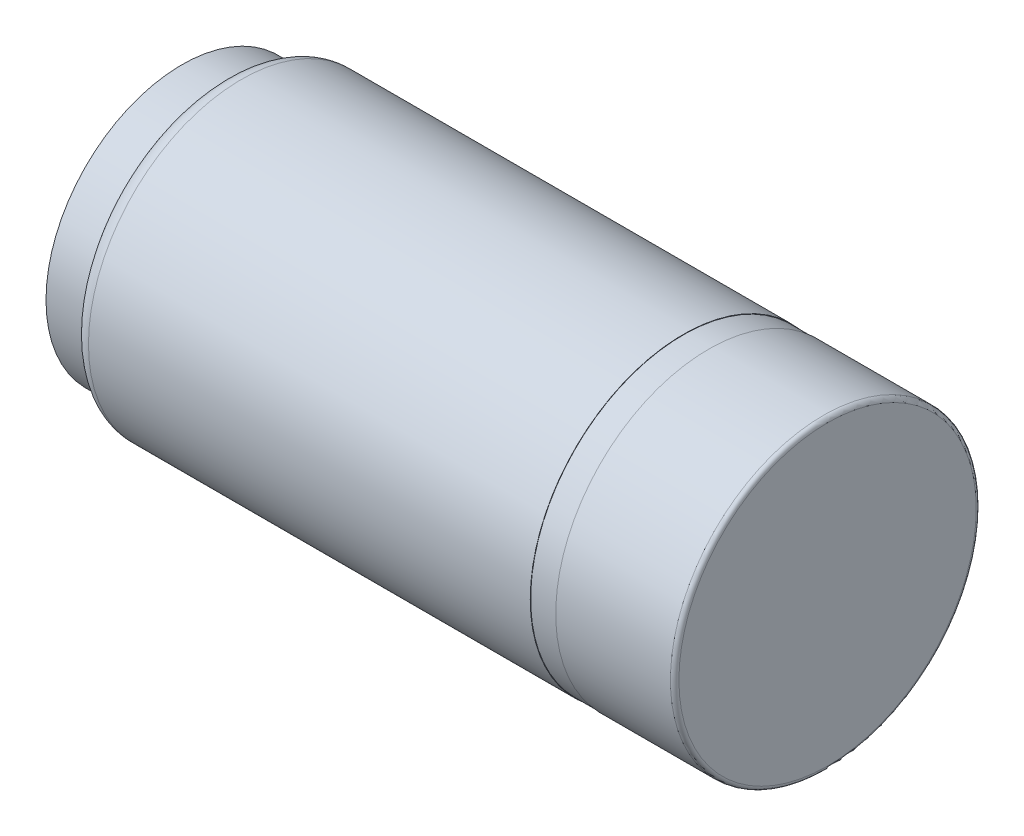
SolidWorks part; units mm, degrees
ref_plane "Спереди" through (0, 0, 0) normal (0, 0, 1) x (1, 0, 0)
ref_plane "Сверху" through (0, 0, 0) normal (0, 1, 0) x (1, 0, 0)
ref_plane "Справа" through (0, 0, 0) normal (1, 0, 0) x (0, 0, -1)
sketch "Эскиз1" plane through (0, 0, 0) normal (0, 1, 0) x (1, 0, 0)
  line L0 (0, 0) -> (104.9, 0) construction
  line L1 (24.3, 16) -> (25.8, 17.5)
  line L2 (0, 0) -> (16.3, 0)
  line L3 (0, 0) -> (0, 3)
  line L4 (0, 3) -> (16.3, 3)
  line L5 (16.3, 0) -> (16.3, 3)
  line L6 (16.3, 0) -> (19.3, 0)
  line L7 (16.3, 0) -> (16.3, 10)
  line L8 (16.3, 10) -> (19.3, 10)
  line L9 (19.3, 0) -> (19.3, 10)
  line L10 (19.3, 0) -> (24.3, 0)
  line L11 (19.3, 0) -> (19.3, 15)
  line L12 (20.3, 16) -> (24.3, 16)
  line L13 (24.3, 0) -> (24.3, 16)
  line L14 (24.3, 0) -> (42.3, 0)
  line L15 (24.3, 0) -> (24.3, 16)
  line L16 (25.8, 17.5) -> (40.8, 17.5)
  line L17 (42.3, 0) -> (42.3, 16)
  line L18 (19.3, 15) -> (20.3, 16)
  line L19 (40.8, 17.5) -> (42.3, 16)
  line L21 (42.3, 0) -> (47.3, 0)
  line L22 (42.3, 0) -> (42.3, 16)
  line L23 (42.3, 16) -> (47.3, 16)
  line L24 (47.3, 0) -> (47.3, 16)
  line L25 (47.3, 0) -> (104.3, 0)
  line L26 (47.3, 0) -> (47.3, 16)
  line L27 (49.3, 18) -> (104.3, 18)
  line L28 (104.3, 0) -> (104.3, 18)
  arc A0 (47.3, 16) -> (49.3, 18) centre (49.3, 16) cw
  point P10 (19.3, 16)
  point P12 (42.3, 17.5)
  point P13 (24.3, 17.5)
  point P28 (47.3, 18)
  dimension "D14" = 2
  dimension "D2" = 3
  dimension "D3" = 16.3
  dimension "D4" = 3
  dimension "D5" = 10
  dimension "D6" = 16
  dimension "D7" = 5
  dimension "D8" = 17.5
  dimension "D9" = 18
  dimension "D10" = 5
  dimension "D11" = 18
  dimension "D12" = 57
  dimension "D15" = 104.3
  dimension "D16" = 31
  dimension "D17" = 88
revolve "Повернуть1 основной корпус" add sketch "Эскиз1" angle 360 about L0
sketch "Эскиз19" plane through (0, 0, 0) normal (0, 1, 0) x (1, 0, 0)
  line L0 (103.0047, 0) -> (0, 0) construction
  line L1 (104.3, 18) -> (101.3, 18)
  line L2 (104.3, 18) -> (104.3, 17.95)
  line L3 (104.3, 17.95) -> (101.3, 17.95)
  line L4 (101.3, 18) -> (101.3, 17.95)
  dimension "D1" = 3
  dimension "D2" = 0.05
revolve "Вырез-Повернуть2 пластиковая часть" cut sketch "Эскиз19" angle 360 about L0
sketch "Эскиз20" plane through (104.3, 0, 0) normal (1, 0, 0) x (0, 0, -1)
  circle A0 centre (0, 0) radius 18
  dimension "D1" = 36
extrude "Бобышка-Вытянуть2 пластиковая крышка контактов" add sketch "Эскиз20" along normal blind 14
sketch "Эскиз11" plane through (16.3, 0, 0) normal (-1, 0, 0) x (0, 0, 1)
  line L0 (-4.3589, 9) -> (4.3589, 9)
  line L1 (4.3589, -9) -> (-4.3589, -9)
  circle A0 centre (0, 0) radius 10 construction
  circle A3 centre (0, 0) radius 10
  circle M1 centre (0, 0) radius 10
  dimension "D1" = 18
  dimension "D2" = 9
extrude "Вырез-Вытянуть6" cut sketch "Эскиз11" against normal blind 3 contours L0 M1 | L1 M1
sketch "Эскиз6" plane through (0, 0, 0) normal (-1, 0, 0) x (0, 0, 1)
  line L0 (1.5611, 2.5618) -> (-1.7531, 2.4345)
  circle A0 centre (0, 0) radius 3
  circle M1 centre (0, 0) radius 3
  dimension "D2" = 6
  dimension "D1" = 2.5
extrude "Вырез-Вытянуть4 на оси" cut sketch "Эскиз6" against normal blind 12 contours L0 M1
sketch "Эскиз13" plane through (19.3, 0, 0) normal (-1, 0, 0) x (0, 0, 1)
  line L0 (0, 0) -> (-9.1924, 9.1924)
  circle A0 centre (0, 0) radius 13
  circle A2 centre (-9.1924, 9.1924) radius 1.5
  dimension "D1" = 26
  dimension "D2" = 3
extrude "Вырез-Вытянуть8 для винтов" cut sketch "Эскиз13" against normal blind 7 contours A0 A2 | L0 A2 A0 | A0 A2 L0
pattern_circular "Круговой массив2 для винтов" count 4 every 90 about axis through (0, 0, 0) along (1, 0, 0) of "Вырез-Вытянуть8 для винтов"
fillet "Скругление1" radius 0.5 16 edges at (19.3, 0, -10) (19.3, 0, 10) (19.3, 0, 15) (19.3, 9.1924, -7.6924) (19.3, -7.6924, -9.1924) (19.3, -9.1924, 7.6924) (19.3, 7.6924, 9.1924) (17.8, 9, 4.3589) (17.8, 9, -4.3589) (16.3, 9, 0) (19.3, 9, 0) (17.8, -9, -4.3589) (17.8, -9, 4.3589) (16.3, -9, 0) (19.3, -9, 0) (118.3, 0, -18)
sketch "Эскиз21" plane through (0, 0, 0) normal (-1, 0, 0) x (0, 0, 1)
  circle A0 centre (0, 0) radius 20
  dimension "D1" = 40
extrude "Вырез-Вытянуть7" cut sketch "Эскиз21" against normal blind 42.3
